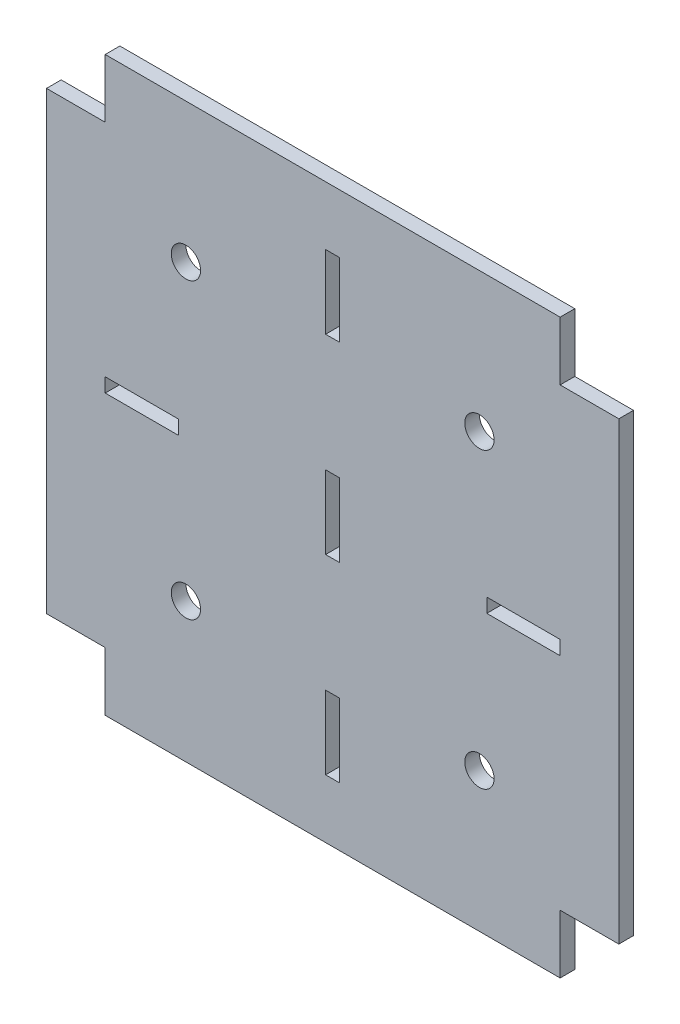
SolidWorks part; units mm, degrees
ref_plane "前基準面" through (0, 0, 0) normal (0, 0, 1) x (1, 0, 0)
ref_plane "上基準面" through (0, 0, 0) normal (0, 1, 0) x (1, 0, 0)
ref_plane "右基準面" through (0, 0, 0) normal (1, 0, 0) x (0, 0, -1)
sketch "草圖1" plane through (0, 0, 0) normal (0, 0, 1) x (1, 0, 0)
  line L0 (0, 0) -> (0, 39) construction
  line L1 (-31, 39) -> (31, 39)
  line L2 (-39, 31) -> (-39, -31)
  line L3 (-31, -39) -> (31, -39)
  line L4 (39, 31) -> (39, -31)
  line L5 (-0.9616, -21) -> (0.9616, -21)
  line L6 (-0.9616, 31) -> (0.9616, 31)
  line L7 (-39, 31) -> (-31, 31)
  line L8 (-31, 39) -> (-31, 31)
  line L9 (-0.9616, 31) -> (-0.9616, 21)
  line L10 (-0.9616, 21) -> (0.9616, 21)
  line L11 (39, 31) -> (31, 31)
  line L12 (31, 39) -> (31, 31)
  line L13 (0.9616, 31) -> (0.9616, 21)
  line L14 (-31, 0.9616) -> (-21, 0.9616)
  line L15 (-39, -31) -> (-31, -31)
  line L16 (-31, -39) -> (-31, -31)
  line L17 (-31, 0.9616) -> (-31, -0.9616)
  line L18 (-31, -0.9616) -> (-21, -0.9616)
  line L19 (39, -31) -> (31, -31)
  line L20 (31, -39) -> (31, -31)
  line L21 (0, 0) -> (-39, 0) construction
  line L22 (-21, 0.9616) -> (-21, -0.9616)
  line L23 (0.9616, -31) -> (0.9616, -21)
  line L24 (-0.9616, -31) -> (0.9616, -31)
  line L25 (-0.9616, -31) -> (-0.9616, -21)
  line L26 (31, 0.9616) -> (31, -0.9616)
  line L27 (21, 0.9616) -> (21, -0.9616)
  line L28 (31, 0.9616) -> (21, 0.9616)
  line L29 (31, -0.9616) -> (21, -0.9616)
  line L30 (-26, 0.9616) -> (-26, -39) construction
  line L31 (-0.9616, 5) -> (0.9616, 5)
  line L32 (-0.9616, 5) -> (-0.9616, -5)
  line L33 (-0.9616, -5) -> (0.9616, -5)
  line L34 (0.9616, 5) -> (0.9616, -5)
  line L35 (-0.9616, -26) -> (39, -26) construction
  circle A0 centre (-20, 20) radius 2
  circle A1 centre (20, 20) radius 2
  circle A2 centre (20, -20) radius 2
  circle A3 centre (-20, -20) radius 2
  point P4 (39, 0)
  point P6 (0, 39)
  point P36 (0, 0)
  point P51 (-39, 0)
  dimension "D11" = 4
  dimension "D1" = 78
  dimension "D2" = 62
  dimension "D3" = 62
  dimension "D4" = 78
  dimension "D5" = 10
  dimension "D6" = 1.9231
  dimension "D7" = 26
  dimension "D8" = 26
  dimension "D9" = 20
  dimension "D10" = 20
  dimension "D14" = 40
  dimension "D15" = 40
  dimension "D12" = 2
  dimension "D13" = 2
extrude "填料-伸長1" add sketch "草圖1" along normal blind 2
